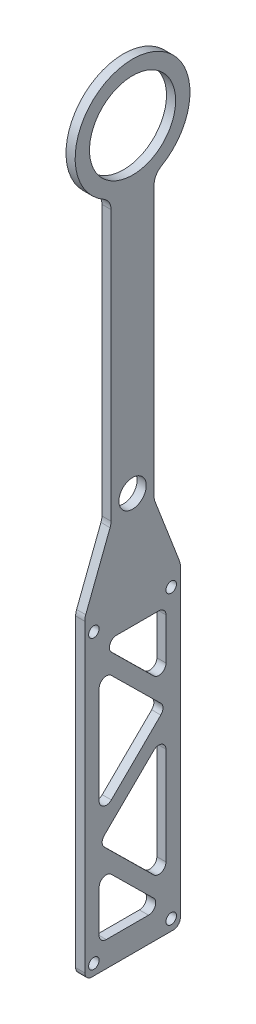
SolidWorks part; units mm, degrees
material "6061 Alloy"
ref_plane "Front Plane" through (0, 0, 0) normal (0, 0, 1) x (1, 0, 0)
ref_plane "Top Plane" through (0, 0, 0) normal (0, 1, 0) x (1, 0, 0)
ref_plane "Right Plane" through (0, 0, 0) normal (1, 0, 0) x (0, 0, -1)
sketch "Sketch1" plane through (0, 0, 0) normal (1, 0, 0) x (0, 0, -1)
  line L0 (-13.4747, 0) -> (13.4747, 0) construction
  line L1 (0, 0) -> (0, 35) construction
  line L2 (-13.4747, 0) -> (0, 35) construction
  line L3 (0, 35) -> (13.4747, 0) construction
  line L4 (13.4747, 0) -> (-13.4747, 0) construction
  line L5 (20.7574, -5) -> (-20.7574, -5)
  line L6 (-20.7574, -5) -> (0, 48.9165)
  line L7 (0, 48.9165) -> (20.7574, -5)
  line L8 (0, 35) -> (0, 146) construction
  line L9 (0, 35) -> (0, 146) construction
  line L12 (-7.5, 35) -> (-7.5, 146)
  line L13 (7.5, 35) -> (7.5, 146)
  line L14 (-7.5, 35) -> (-7.5, 29.4356)
  line L15 (7.5, 35) -> (7.5, 29.4356)
  line L16 (-13.4747, 0) -> (13.4747, 0) construction
  line L17 (-13.4747, 0) -> (-13.4747, -100) construction
  line L18 (13.4747, 0) -> (13.4747, -100) construction
  line L19 (-13.4747, -100) -> (13.4747, -100) construction
  line L20 (-20.7574, -5) -> (20.7574, -5)
  line L21 (-20.7574, -5) -> (-20.7574, -103.81)
  line L22 (20.7574, -5) -> (20.7574, -103.81)
  line L23 (-20.7574, -103.81) -> (20.7574, -103.81)
  circle A0 centre (-13.4747, 0) radius 1.8288
  circle A1 centre (0, 35) radius 4.7625
  circle A2 centre (13.4747, 0) radius 1.8288
  circle A3 centre (0, 146) radius 3 construction
  arc A6 (-7.5, 35) -> (7.5, 35) centre (0, 35) ccw
  arc A7 (7.5, 146) -> (-7.5, 146) centre (0, 146) ccw
  circle A8 centre (-13.4747, -100) radius 1.8288
  circle A9 centre (13.4747, -100) radius 1.8288
  circle A17 centre (0, 146) radius 15
  circle A18 centre (0, 146) radius 20
  point P4 (0, 0)
  point P14 (0, 90.5)
  point P34 (0, 146)
  dimension "D3" = 3.6576
  dimension "D4" = 9.525
  dimension "D7" = 6
  dimension "D13" = 30
  dimension "D14" = 40
  dimension "D1" = 26.9494
  dimension "D5" = 111
  dimension "D6" = 15
  dimension "D8" = 100
  dimension "D9" = 3.81
  dimension "D10" = 35
  dimension "D2" = 5
extrude "Boss-Extrude1" add sketch "Sketch1" along normal blind 3.175 contours L21 L23 L22 L5 A9 A8 | A6 L6 L5 L7 A2 A0 | L6 A6 L7 A1 | A18 L12 A6 L6 L7 L13 | A6 L7 L15 | A6 L14 L6 | L12 A18 L13 A17 | L13 A18 L12 A17 region at (0, -54.1702, 0) region at (0, 9.5725, 0) region at (0, 31.6598, -7.2402) region at (0, 31.6598, 7.2402) region at (0, 27.7524, 0) region at (0, 82.7884, 0) region at (0, 129.0809, 0) region at (0, 130.2346, -8.0555)
sketch "Sketch2" plane through (3.175, 0, 0) normal (1, 0, 0) x (0, 0, -1)
  line L0 (-11.645, -5) -> (11.645, -5) construction
  line L1 (-11.645, -95) -> (11.645, -95) construction
  line L2 (11.645, -95) -> (11.645, -5) construction
  line L3 (-11.645, -95) -> (-11.645, -5) construction
  line L6 (11.645, -38.5118) -> (-11.645, -61.4882) construction
  line L7 (11.645, -5) -> (-11.645, -5)
  line L8 (-11.645, -5) -> (11.645, -27.9764)
  line L9 (11.645, -27.9764) -> (11.645, -5)
  line L10 (-11.645, -12.0236) -> (11.645, -35)
  line L11 (11.645, -35) -> (-11.645, -57.9764)
  line L12 (-11.645, -57.9764) -> (-11.645, -35)
  line L13 (-11.645, -35) -> (-11.645, -12.0236)
  line L14 (-11.645, -72.0236) -> (-11.645, -95)
  line L15 (-11.645, -95) -> (11.645, -95)
  line L16 (11.645, -95) -> (-11.645, -72.0236)
  line L17 (11.645, -42.0236) -> (11.645, -65)
  line L18 (11.645, -65) -> (11.645, -87.9764)
  line L19 (11.645, -87.9764) -> (-11.645, -65)
  line L20 (-11.645, -65) -> (11.645, -42.0236)
  line L21 (16.645, -1056.0877) -> (16.645, 48943.9123) construction
  line L22 (-16.645, -1060.2922) -> (-16.645, 48939.7078) construction
  line L23 (16.645, 30.2375) -> (-16.645, 30.2375) construction
  line L24 (-20.7574, -103.81) -> (-16.645, -103.81)
  line L25 (-20.7574, -103.81) -> (-20.7574, 30.2375)
  line L26 (-16.645, -103.81) -> (-16.645, 30.2375)
  line L27 (-20.7574, 30.2375) -> (-16.645, 30.2375)
  line L28 (-20.7574, -103.81) -> (20.7574, -103.81) construction
  line L29 (20.7574, -103.81) -> (16.645, -103.81)
  line L30 (20.7574, -103.81) -> (20.7574, 30.2375)
  line L31 (16.645, -103.81) -> (16.645, 30.2375)
  line L32 (20.7574, 30.2375) -> (16.645, 30.2375)
  circle A0 centre (13.4747, 0) radius 1.8288 construction
  circle A1 centre (13.4747, -100) radius 1.8288 construction
  circle A2 centre (0, 35) radius 4.7625 construction
  point P6 (11.645, -50)
  point P10 (0, 30.2375)
  point P21 (0, -50)
  dimension "D1" = 33.29
  dimension "D2" = 5
  dimension "D3" = 5
  dimension "D4" = 5
  dimension "D5" = 5
  dimension "D6" = 2.5
  dimension "D8" = 5
  dimension "D7" = 2
extrude "Cut-Extrude1" cut sketch "Sketch2" against normal up to next
fillet "Fillet3" radius 2.5 14 edges at (1.5875, -57.9764, 11.645) (1.5875, -35, -11.645) (1.5875, -95, -11.645) (1.5875, -72.0236, 11.645) (1.5875, -95, 11.645) (1.5875, -27.9764, -11.645) (1.5875, -5, -11.645) (1.5875, -12.0236, 11.645) (1.5875, -5, 11.645) (1.5875, -87.9764, -11.645) (1.5875, -42.0236, -11.645) (1.5875, -65, 11.645) (1.5875, -103.81, -16.645) (1.5875, -103.81, 16.645)
fillet "Fillet4" radius 5 6 edges at (1.5875, 29.4356, -7.5) (1.5875, 29.4356, 7.5) (1.5875, 5.6818, 16.645) (1.5875, 5.6818, -16.645) (1.5875, 127.4595, -7.5) (1.5875, 127.4595, 7.5)
